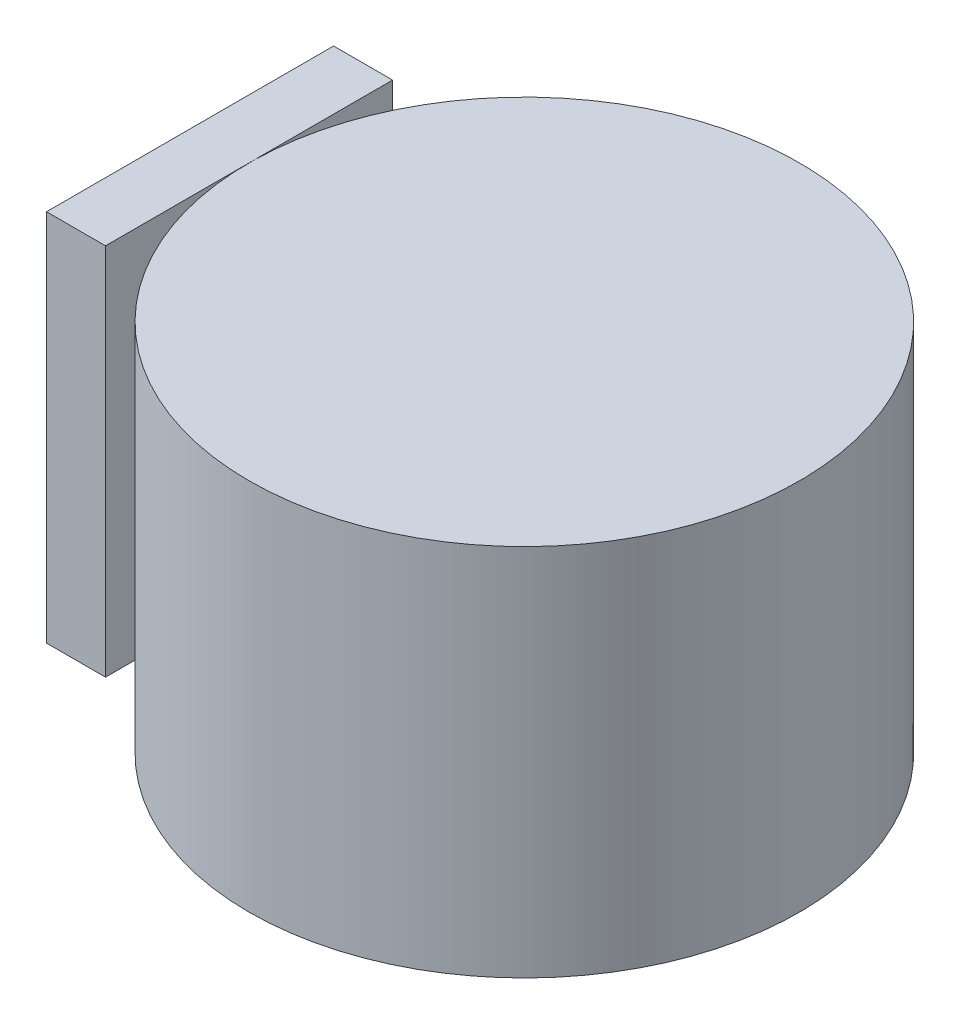
SolidWorks part; units mm, degrees
ref_plane "前视基准面" through (0, 0, 0) normal (0, 0, 1) x (1, 0, 0)
ref_plane "上视基准面" through (0, 0, 0) normal (0, 1, 0) x (1, 0, 0)
ref_plane "右视基准面" through (0, 0, 0) normal (1, 0, 0) x (0, 0, -1)
sketch "草图1" plane through (0, 0, 0) normal (0, 1, 0) x (1, 0, 0)
  circle A0 centre (0, 0) radius 14
extrude "凸台-拉伸1" add sketch "草图1" along normal blind 19
sketch "草图2" plane through (0, 0, 0) normal (1, 0, 0) x (0, 0, -1)
  line L1 (-3, 24) -> (-1.5, 24)
  line L2 (-3, 24) -> (-3, 30)
  line L3 (-3, 30) -> (-1.5, 30)
  line L4 (-1.5, 24) -> (-1.5, 30)
sketch "草图3" plane through (0, 0, 0) normal (0, 0, 1) x (1, 0, 0)
  line L1 (-17, 0) -> (-14, 0)
  line L2 (-17, 0) -> (-17, 19)
  line L3 (-17, 19) -> (-14, 19)
  line L4 (-14, 0) -> (-14, 19)
extrude "凸台-拉伸2" add sketch "草图3" along normal blind 7.3 and the other way blind 7.3
